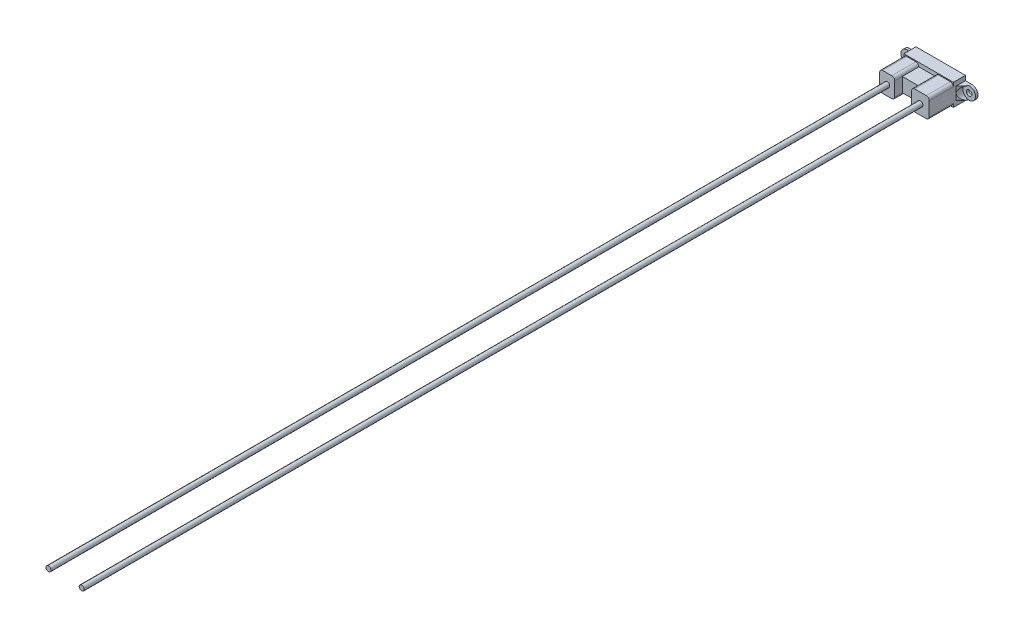
SolidWorks part; units mm, degrees
ref_plane "前视基准面" through (0, 0, 0) normal (0, 0, 1) x (1, 0, 0)
ref_plane "上视基准面" through (0, 0, 0) normal (0, 1, 0) x (1, 0, 0)
ref_plane "右视基准面" through (0, 0, 0) normal (1, 0, 0) x (0, 0, -1)
other "Configuration Table"
sketch "草图1" plane through (0, 0, 0) normal (0, 0, 1) x (1, 0, 0)
  line L1 (14.75, -6.5) -> (4.675, -6.5)
  line L2 (14.75, -6.5) -> (14.75, 6.5)
  line L3 (14.75, 6.5) -> (-14.75, 6.5)
  line L4 (-14.75, -6.5) -> (-14.75, 6.5)
  line L5 (14.75, -6.5) -> (-14.75, 6.5) construction
  line L6 (14.75, 6.5) -> (-14.75, -6.5) construction
  line L10 (-5.425, -6.5) -> (-5.425, -4.2)
  line L11 (-5.425, -4.2) -> (4.675, -4.2)
  line L12 (4.675, -4.2) -> (4.675, -6.5)
  line L13 (-5.425, -6.5) -> (-14.75, -6.5)
  point P0 (0, 0)
  dimension "D1" = 13
  dimension "D2" = 29.5
  dimension "D3" = 9.325
  dimension "D4" = 2.3
  dimension "D5" = 10.1
extrude "凸台-拉伸1" add sketch "草图1" along normal blind 7.2
sketch "草图2" plane through (0, 0, 0) normal (0, 0, 1) x (1, 0, 0)
  line L1 (-14.75, 6.5) -> (-14.75, -6.5) construction
  line L2 (-18.5, 3.75) -> (-14.75, 3.75)
  line L3 (-14.75, 3.75) -> (-14.75, -3.75)
  line L4 (-14.75, -3.75) -> (-18.5, -3.75)
  line L5 (14.75, -6.5) -> (14.75, 6.5) construction
  line L6 (18.5, 3.75) -> (14.75, 3.75)
  line L7 (14.75, 3.75) -> (14.75, 0)
  line L8 (18.5, -3.75) -> (14.75, -3.75)
  line L9 (14.75, -3.75) -> (14.75, 0)
  arc A0 (-18.5, 3.75) -> (-18.5, -3.75) centre (-18.5, 0) ccw
  arc A1 (18.5, -3.75) -> (18.5, 3.75) centre (18.5, 0) ccw
  circle A2 centre (-18.5, 0) radius 1.6
  circle A3 centre (18.5, 0) radius 1.6
extrude "凸台-拉伸2" add sketch "草图2" along normal blind 1.5
sketch "草图3" plane through (0, 3.75, 0) normal (0, 1, 0) x (1, 0, 0)
  line L6 (-14.75, -1.5) -> (-14.75, -5.5)
  line L7 (-14.75, -7.2) -> (-14.75, 0) construction
  line L8 (-14.75, -5.5) -> (-17.5784, -2.6716)
  line L9 (-17.5784, -2.6716) -> (-18.0123, -1.5)
  line L10 (-14.75, -1.5) -> (-18.5, -1.5) construction
  line L11 (-14.75, -1.5) -> (-18.0123, -1.5)
extrude "凸台-拉伸3" add sketch "草图3" against normal up to vertex (7.5 mm away) up to point (-18.5, -3.75, 1.5)
sketch "草图5" plane through (-5.425, 0, 0) normal (1, 0, 0) x (0, 0, -1)
  line L2 (-7.2, -4.2) -> (0, -4.2) construction
  line L3 (-3.9, -4.2) -> (-2.7, -4.2)
  line L4 (-2.7, -4.2) -> (-2.7, -6.5)
  line L5 (-7.2, -6.5) -> (0, -6.5) construction
  line L6 (-2.7, -6.5) -> (-2.7, -12.4)
  line L7 (-2.7, -12.4) -> (-3.9, -12.4)
  line L8 (-3.9, -12.4) -> (-3.9, -4.2)
extrude "凸台-拉伸4" add sketch "草图5" along normal up to vertex (10.1 mm away) up to point (4.675, -6.5, 7.2)
sketch "草图7" plane through (0, 0, 1.5) normal (0, 0, 1) x (1, 0, 0)
  line L0 (-18.0123, 1.5238) -> (-18.0123, -1.5238)
  circle A0 centre (-18.5, 0) radius 3.75
  arc A1 (-18.0123, 1.5238) -> (-18.0123, -1.5238) centre (-18.5, 0) ccw
extrude "切除-拉伸3" cut sketch "草图7" along normal blind 21.5
mirror "镜向2" about plane through (0, 0, 0) normal (1, 0, 0) of "凸台-拉伸3", "切除-拉伸3"
sketch "草图8" plane through (0, 0, 7.2) normal (0, 0, 1) x (1, 0, 0)
  line L0 (-14.75, 0) -> (-14.75, 5.95)
  line L1 (-14.75, 6.5) -> (-14.75, -6.5) construction
  line L2 (-14.75, 5.95) -> (-5.8, 5.95)
  line L3 (-5.8, 5.95) -> (-5.8, -5.95)
  line L4 (-5.8, -5.95) -> (-14.75, -5.95)
  line L5 (-14.75, -5.95) -> (-14.75, 0)
  line L6 (14.75, -5.95) -> (4.3, -5.95)
  line L7 (14.75, -6.5) -> (14.75, 6.5) construction
  line L8 (4.3, -5.95) -> (4.3, 5.95)
  line L9 (4.3, 5.95) -> (14.75, 5.95)
  line L10 (14.75, 5.95) -> (14.75, -5.95)
extrude "凸台-拉伸5" add sketch "草图8" along normal blind 14.4
fillet "圆角1" radius 1.75 8 edges at (-5.8, -5.95, 14.4) (-14.75, -5.95, 14.4) (-14.75, 5.95, 14.4) (-5.8, 5.95, 14.4) (14.75, 5.95, 14.4) (4.3, 5.95, 14.4) (4.3, -5.95, 14.4) (14.75, -5.95, 14.4)
sketch "草图9" plane through (0, 0, 7.2) normal (0, 0, 1) x (1, 0, 0)
  line L0 (-5.8, 0) -> (-5.8, 4.2)
  line L1 (-5.8, -4.2) -> (-5.8, 4.2) construction
  line L2 (-5.8, -4.2) -> (-5.8, 4.2) construction
  line L3 (-5.8, 4.2) -> (4.3, 4.2)
  line L4 (4.3, 4.2) -> (4.3, -4.2) construction
  line L5 (4.3, 4.2) -> (4.3, -4.2)
  line L6 (4.3, 4.2) -> (4.3, -4.2) construction
  line L7 (4.3, -4.2) -> (-5.8, -4.2)
  line L8 (-5.8, -4.2) -> (-5.8, 0)
extrude "凸台-拉伸6" add sketch "草图9" along normal blind 9.9
sketch "草图10" plane through (0, 0, 3.9) normal (0, 0, 1) x (1, 0, 0)
  line L0 (-4.425, -12.4) -> (3.675, -12.4)
  line L1 (4.675, -4.2) -> (-5.425, -4.2) construction
  line L2 (-4.425, -4.2) -> (-4.425, -12.4)
  line L3 (4.675, -12.4) -> (-5.425, -12.4) construction
  line L5 (3.675, -12.4) -> (3.675, -4.2)
  line L6 (3.675, -4.2) -> (-4.425, -4.2)
extrude "凸台-拉伸7" add sketch "草图10" along normal blind 5
sketch "草图11" plane through (0, -12.4, 0) normal (0, -1, 0) x (1, 0, 0)
  line L0 (-4.225, 8.7) -> (-4.225, 4.1)
  line L5 (-4.225, 4.1) -> (3.475, 4.1)
  line L6 (3.475, 8.7) -> (3.475, 4.1)
  line L7 (-4.225, 8.7) -> (3.475, 8.7)
extrude "切除-拉伸4" cut sketch "草图11" against normal up to vertex (8.2 mm away) up to point (3.675, -4.2, 8.9)
sketch "草图13" plane through (0, 0, 21.6) normal (0, 0, 1) x (1, 0, 0)
  circle A4 centre (-10.275, 0) radius 1.5
  circle A5 centre (9.525, 0) radius 1.5
extrude "凸台-拉伸9" add sketch "草图13" along normal blind 500
sketch "草图14" plane through (14.75, 0, 0) normal (1, 0, 0) x (0, 0, -1)
  line L1 (-533.254, 12.3278) -> (-136.3951, 12.3278)
  line L2 (-533.254, 12.3278) -> (-533.254, -8.7701)
  line L3 (-533.254, -8.7701) -> (-136.3951, -8.7701)
  line L4 (-136.3951, 12.3278) -> (-136.3951, -8.7701)
